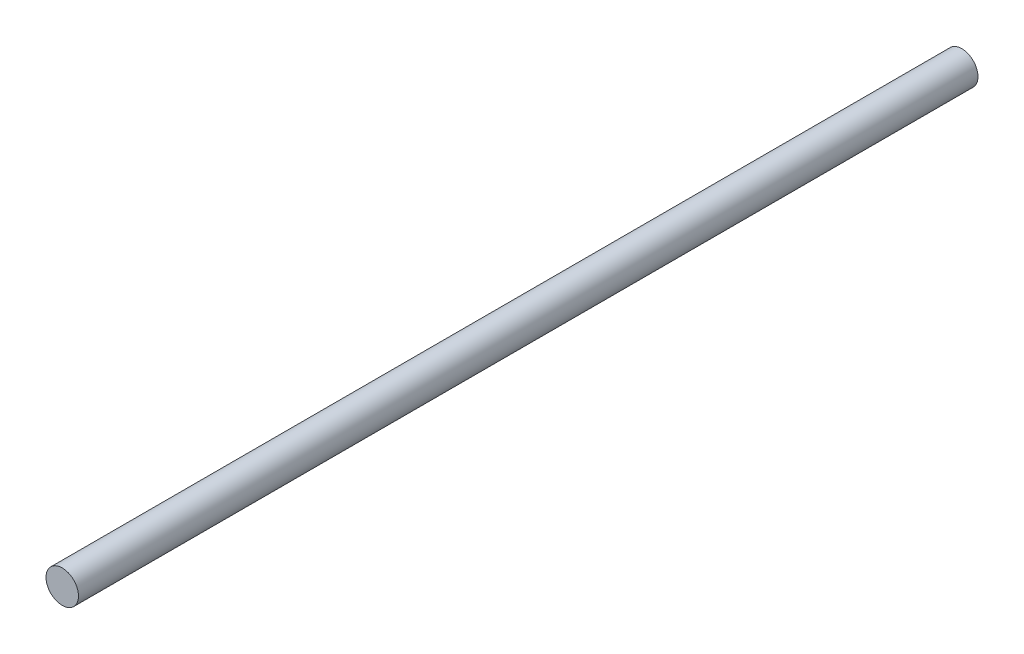
SolidWorks part; units mm, degrees
material "6061-T6 (SS)"
ref_plane "Front Plane" through (0, 0, 0) normal (0, 0, 1) x (1, 0, 0)
ref_plane "Top Plane" through (0, 0, 0) normal (0, 1, 0) x (1, 0, 0)
ref_plane "Right Plane" through (0, 0, 0) normal (1, 0, 0) x (0, 0, -1)
sketch "Sketch1" plane through (0, 0, 0) normal (1, 0, 0) x (0, 0, -1)
  line L0 (0, 0) -> (-0.4031, 2.286)
  line L1 (-0.4031, 2.286) -> (-127, 2.286)
  line L2 (-127, 2.286) -> (-127, 0)
  line L3 (-127, 0) -> (0, 0)
  line L4 (3.9422, 0) -> (-151.6013, 0) construction
  dimension "D1" = 4.572
  dimension "D2" = 127
  dimension "D3" = 80
revolve "Revolve1" add sketch "Sketch1" angle 360 about L4
ref_axis "Axis1" through (0, 0, 127) along (0, 0, -1)
